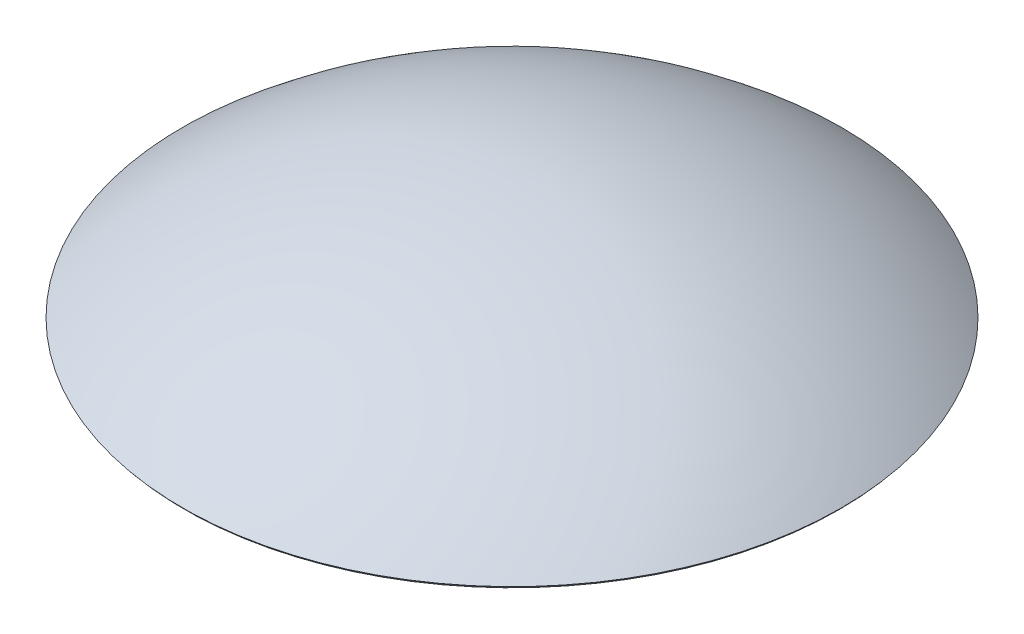
SolidWorks part; units mm, degrees
ref_plane "Front Plane" through (0, 0, 0) normal (0, 0, 1) x (1, 0, 0)
ref_plane "Top Plane" through (0, 0, 0) normal (0, 1, 0) x (1, 0, 0)
ref_plane "Right Plane" through (0, 0, 0) normal (1, 0, 0) x (0, 0, -1)
sketch "Sketch1" plane through (0, 0, 0) normal (0, 0, 1) x (1, 0, 0)
  line L0 (0, 246.825) -> (0, 250)
  line L2 (-141.573, 202.1872) -> (-142.4836, 203.4876)
  line L3 (-159.6765, 190.295) -> (-160.6969, 191.5111)
  arc A0 (0, 250) -> (-160.6969, 191.5111) centre (0, 0) ccw
  arc A1 (0, 246.825) -> (-141.573, 202.1872) centre (0, 0) ccw
  arc A3 (-142.4836, 203.4876) -> (-159.6765, 190.295) centre (0, 0) ccw
  dimension "D1" = 500
  dimension "D2" = 493.65
  dimension "D4" = 5
  dimension "D5" = 35
revolve "Revolve1" add sketch "Sketch1" angle 360 about L0
